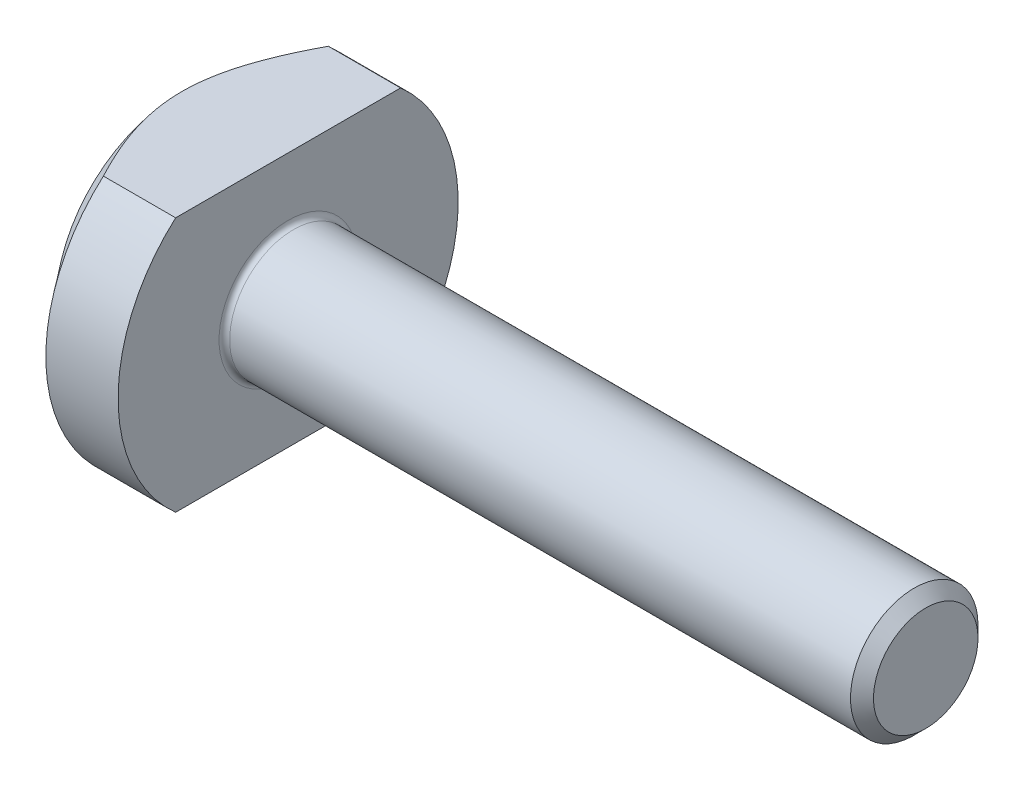
SolidWorks part; units mm, degrees
ref_plane "Front" through (0, 0, 0) normal (0, 0, 1) x (1, 0, 0)
ref_plane "Top" through (0, 0, 0) normal (0, 1, 0) x (1, 0, 0)
ref_plane "Right" through (0, 0, 0) normal (1, 0, 0) x (0, 0, -1)
sketch "Sketch1" plane through (-1.5176, 0, -6.4824) normal (0, 1, 0) x (0, 0, -1)
  line L0 (-6.4824, -1.5176) -> (-14.4824, -1.5176)
  line L1 (-14.4824, -1.5176) -> (-14.4824, 1.8824)
  line L2 (-12.1824, 3.7224) -> (-6.4824, 3.7224)
  line L3 (-6.4824, 3.7224) -> (-6.4824, -1.5176)
  line L4 (-6.4824, 5.8737) -> (-6.4824, -3.9441) construction
  line L5 (-12.1824, 3.7224) -> (-14.4824, 1.8824)
  dimension "D1" = 16
revolve "BaseHead" add sketch "Sketch1" angle 360 about L4
sketch "Sketch2" plane through (0, 0, 0) normal (1, 0, 0) x (0, 0, -1)
  line L0 (5.2915, 6) -> (-5.2915, 6)
  line L3 (5.2915, -6) -> (-5.2915, -6)
  arc A1 (5.2915, 6) -> (-5.2915, 6) centre (0, 0) ccw
  arc A2 (-5.2915, -6) -> (5.2915, -6) centre (0, 0) ccw
  circle A3 centre (0, 0) radius 8 construction
  dimension "D2" = 6
extrude "Cut-Extrude1" cut sketch "Sketch2" against normal through all
sketch "Sketch3" plane through (0, -0.7254, 3.537) normal (1, 0, 0) x (0, 0, -1)
  circle A0 centre (3.537, 0.7254) radius 3
extrude "BaseBody" add sketch "Sketch3" along normal blind 30
cosmetic thread "ThreadCosmetic1" [suppressed] parameters "Lb"=17.4585, "D2"=4.917
ref_plane "Plane1" through (12, 0, 0) normal (1, 0, 0) x (0, 0, -1)
fillet "HeadFillet" radius 0.25 1 edges at (0, 0, -3)
chamfer "Chamfer1" distance 0.5415 angle 45 1 edges at (30, 0, -3)
sketch "Sketch4" [suppressed] plane through (0, 0, 0) normal (0, 1, 0) x (1, 0, 0)
  line L0 (28.917, 3.5415) -> (29.4585, 3.5415)
  line L1 (29.4585, 3.5415) -> (29.4585, 3)
  line L2 (29.4585, 3) -> (29.1877, 2.531)
  line L3 (29.1877, 2.531) -> (28.917, 3)
  line L4 (28.917, 3) -> (28.917, 3.5415)
  line L5 (29.4585, 3) -> (29.4585, -3) construction
  line L6 (29.4585, 3) -> (0.25, 3) construction
  dimension "D1" = 0.5415
revolve "Cut-Revolve10" [suppressed] cut sketch "Sketch4" angle 360
pattern_linear "LPattern10" [suppressed] count 27 of bodies 104
equation "\"D2@Sketch2\" = \"s@Sketch2\" / 2"
equation "\"C1@Chamfer1\" =  ( \"d@Sketch3\" - \"D2@ThreadCosmetic1\" ) / 2 "
equation "\"Lb@ThreadCosmetic1\" = \"b@Plane1\" - \"C1@Chamfer1\""
equation "\"D1@Sketch4\" =  ( \"d@Sketch3\" - \"D2@ThreadCosmetic1\" )  / 2"
equation "\"pitch@LPattern10\" = 1.2 * \"D1@Sketch4\""
equation " \"D1@LPattern10\" = \"Lb@ThreadCosmetic1\" / \"pitch@LPattern10\""
equation "\"D@Sketch1\" = 0.95 * \"s@Sketch2\""
